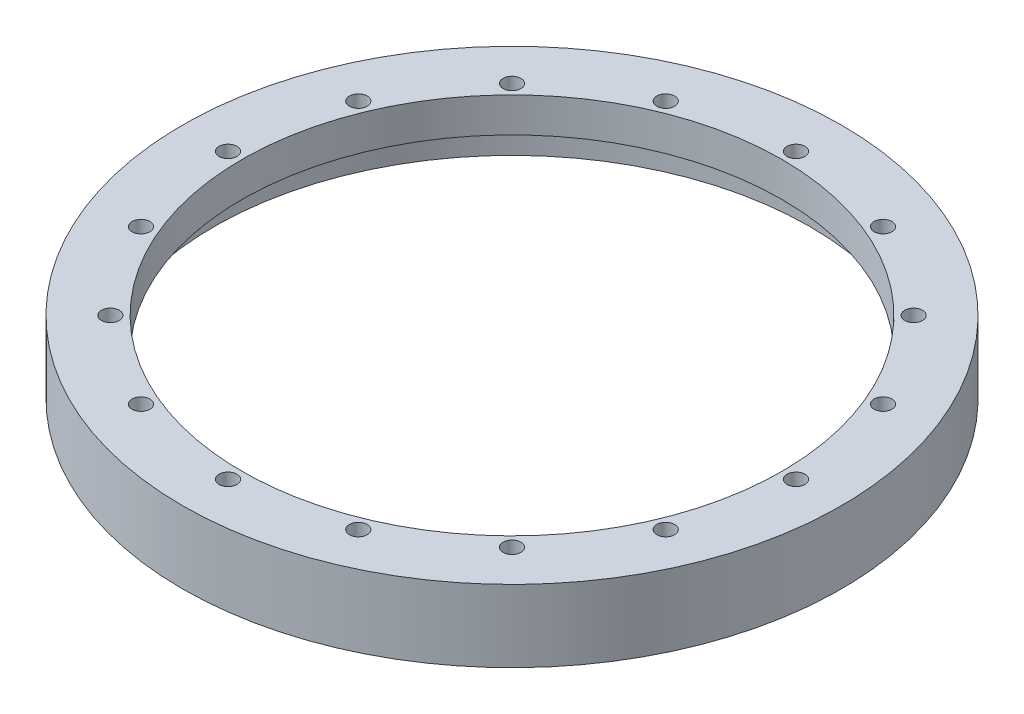
SolidWorks part; units mm, degrees
material "6061-T6 (SS)"
ref_plane "Front Plane" through (0, 0, 0) normal (0, 0, 1) x (1, 0, 0)
ref_plane "Top Plane" through (0, 0, 0) normal (0, 1, 0) x (1, 0, 0)
ref_plane "Right Plane" through (0, 0, 0) normal (1, 0, 0) x (0, 0, -1)
sketch "Sketch1" plane through (0, 0, 0) normal (0, 0, 1) x (1, 0, 0)
  line L0 (-49.4665, 0) -> (-60.3631, 0)
  line L1 (-60.3631, 0) -> (-60.3631, -13.208)
  line L2 (-60.3631, -13.208) -> (-54.5719, -13.208)
  line L3 (-54.5719, -13.208) -> (-54.5719, -6.35)
  line L4 (-54.5719, -6.35) -> (-49.4665, -6.35)
  line L5 (-49.4665, -6.35) -> (-49.4665, 0)
  line L6 (0, 0) -> (0, 8.0765) construction
  dimension "D1" = 49.4665
  dimension "D2" = 54.5719
  dimension "D3" = 60.3631
  dimension "D4" = 13.208
  dimension "D5" = 6.35
revolve "Revolve1" add sketch "Sketch1" angle 360 about L6
sketch "Sketch2" plane through (0, 0, 0) normal (0, 1, 0) x (1, 0, 0)
  line L0 (0, 49.4665) -> (0, 52.0192) construction
  circle A0 centre (0, 0) radius 49.4665 construction
  dimension "D1" = 52.0192
hole_wizard "#4 Clearance Hole1" positions "3DSketch1" profile "Sketch3" hole size "#4" standard "Ansi Inch"
sketch3d "3DSketch1"
  point P0 (0, 0, -52.0192)
sketch "Sketch3" plane through (0, 0, -52.0192) normal (1, 0, 0) x (0, 0, 1)
  line L0 (0, 0) -> (0, 11.1406)
  line L1 (0, 11.1406) -> (1.6319, 10.16)
  line L2 (1.6319, 10.16) -> (1.6319, 0)
  line L5 (1.6319, 0) -> (0, 0)
  line L10 (0, 11.1406) -> (-1.632, 10.16) construction
  line L11 (0, -6.35) -> (0, 107.95) construction
  dimension "Hole Dia." = 3.2639
  dimension "Hole Depth" = 10.16
  dimension "Drill Angle" = 118
pattern_circular "CirPattern1" count 16 over 360 about axis through (0, 0, 0) along (0, -1, 0) of "#4 Clearance Hole1"
sketch "Sketch4" plane through (0, 0, 0) normal (0, 1, 0) x (1, 0, 0)
  line L0 (0, 0) -> (8.8571, 59.7098) construction
  line L1 (0, 0) -> (14.667, 58.5541) construction
  line L3 (0, 0) -> (0, 49.4665) construction
  line L4 (8.8571, 59.7098) -> (7.2582, 48.9311)
  line L5 (14.667, 58.5541) -> (12.0194, 47.9841)
  arc A0 (7.2582, 48.9311) -> (12.0194, 47.9841) centre (0, 0) cw
  circle A1 centre (0, 0) radius 49.4665 construction
  arc A2 (8.8571, 59.7098) -> (14.667, 58.5541) centre (0, 0) cw
  circle A3 centre (0, 0) radius 60.3631 construction
  dimension "D1" = 5.625
  dimension "D2" = 8.438
